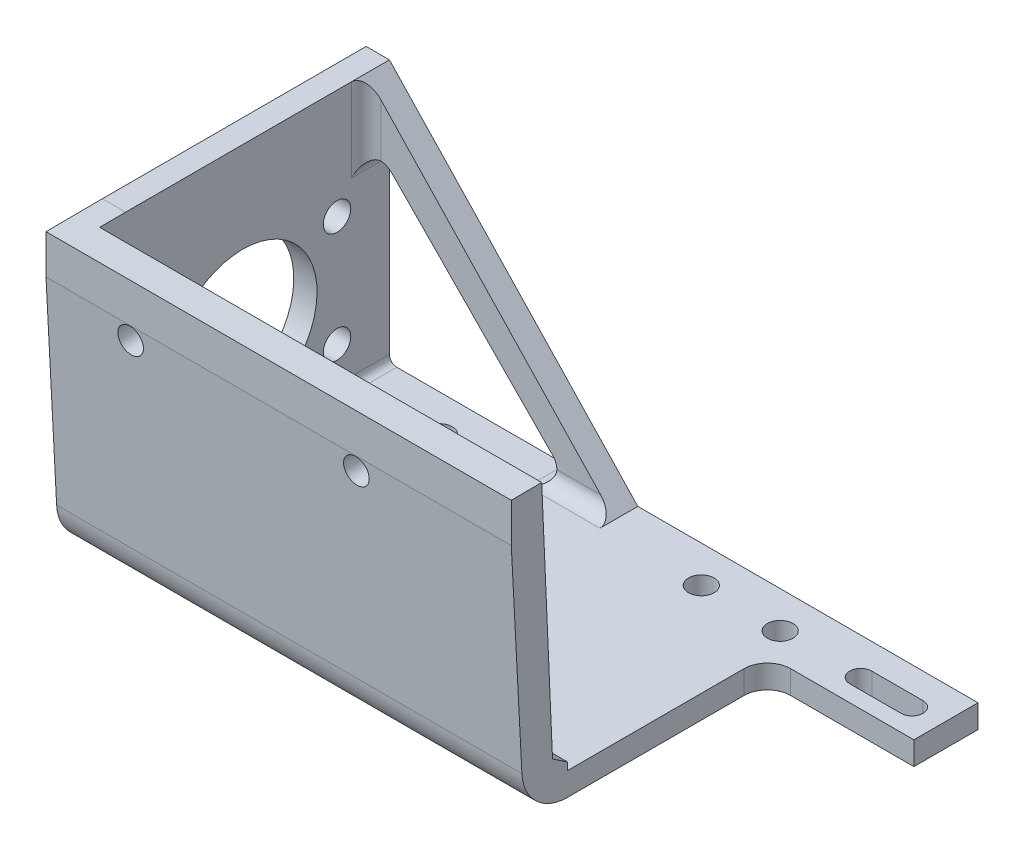
SolidWorks part; units mm, degrees
ref_plane "Front Plane" through (0, 0, 0) normal (0, 0, 1) x (1, 0, 0)
ref_plane "Top Plane" through (0, 0, 0) normal (0, 1, 0) x (1, 0, 0)
ref_plane "Right Plane" through (0, 0, 0) normal (1, 0, 0) x (0, 0, -1)
sketch "Sketch2" plane through (0, 0, 0) normal (0, 0, 1) x (1, 0, 0)
  line L0 (6.35, 78) -> (80, 0.1684)
  line L1 (0, 0) -> (6.35, 0)
  line L2 (0, 0) -> (0, 78)
  line L3 (0, 78) -> (6.35, 78)
  line L4 (6.35, 0) -> (6.35, 65.0327)
  line L6 (6.35, 65.0327) -> (70, 0.1684)
  line L7 (70, 0.1684) -> (80, 0.1684)
  dimension "D1" = 6.35
  dimension "D2" = 78
  dimension "D3" = 80
  dimension "D4" = 10
extrude "Boss-Extrude1" add sketch "Sketch2" along normal blind 80
sketch "Sketch3" plane through (6.35, 0, 0) normal (1, 0, 0) x (0, 0, -1)
  line L0 (0, 0) -> (0, 65.0327) construction
  line L1 (-80, 0) -> (0, 0)
  line L2 (-80, 0) -> (-80, 6.35)
  line L3 (-80, 6.35) -> (0, 6.35)
  line L4 (0, 0) -> (0, 6.35)
  dimension "D1" = 6.35
extrude "Boss-Extrude2" add sketch "Sketch3" along normal blind 160.65
sketch "Sketch8" plane through (0, 6.35, 0) normal (0, 1, 0) x (1, 0, 0)
  line L0 (167, 0) -> (74.1505, 0) construction
  line L1 (6.35, -80) -> (94.6764, -80)
  line L2 (6.35, -80) -> (6.35, -6.35)
  line L3 (6.35, -6.35) -> (94.6764, -6.35)
  line L4 (94.6764, -80) -> (94.6764, -6.35)
  dimension "D1" = 6.35
extrude "Cut-Extrude2" cut sketch "Sketch8" along normal up to next
sketch "Sketch9" plane through (0, 6.35, 0) normal (0, 1, 0) x (1, 0, 0)
  line L1 (167, -80) -> (0, -80)
  line L2 (167, -80) -> (167, -72)
  line L3 (167, -72) -> (0, -72)
  line L4 (0, -80) -> (0, -72)
extrude "Cut-Extrude4" cut sketch "Sketch9" against normal through all both and the other way through all
sketch "Sketch10" plane through (0, 6.35, 0) normal (0, 1, 0) x (1, 0, 0)
  line L0 (167, 0) -> (74.1505, 0) construction
  line L1 (167, -72) -> (127, -72)
  line L2 (167, -72) -> (167, -17.5)
  line L3 (167, -17.5) -> (127, -17.5)
  line L4 (127, -72) -> (127, -17.5)
  dimension "D1" = 17.5
extrude "Cut-Extrude5" cut sketch "Sketch10" against normal up to next
sketch "Sketch11" plane through (0, 6.35, 0) normal (0, 1, 0) x (1, 0, 0)
  line L0 (159, -10) -> (145, -10) construction
  line L1 (159, -13) -> (145, -13)
  line L2 (159, -7) -> (145, -7)
  line L3 (167, 0) -> (167, -17.5) construction
  line L4 (167, 0) -> (74.1505, 0) construction
  line L5 (0, -72) -> (0, 0) construction
  arc A0 (159, -13) -> (159, -7) centre (159, -10) ccw
  arc A1 (145, -7) -> (145, -13) centre (145, -10) ccw
  circle A2 centre (123, -10) radius 3.5
  circle A3 centre (101.48, -10) radius 3.5
  circle A6 centre (101.48, -62) radius 3.5
  circle A9 centre (30, -10) radius 3.5
  point P2 (152, -10)
  point P7 (162, -10)
  point P18 (0, 0)
  dimension "D1" = 14
  dimension "D4" = 30
  dimension "D5" = 22
  dimension "D9" = 65.52
  dimension "D2" = 5
  dimension "D3" = 7
extrude "Cut-Extrude6" cut sketch "Sketch11" against normal up to next
sketch "Sketch12" plane through (6.35, 0, 0) normal (1, 0, 0) x (0, 0, -1)
  line L0 (0, 6.35) -> (0, 65.0327) construction
  line L2 (0, 6.35) -> (-72, 6.35) construction
  circle A0 centre (-66.64, 15.3315) radius 3.75
  circle A1 centre (-66.64, 48.1711) radius 3.75
  circle A2 centre (-14.3, 48.12) radius 3.75
  circle A3 centre (-14.3, 17.9) radius 3.75
  circle A4 centre (-40, 33) radius 20.25
  dimension "D1" = 40
  dimension "D2" = 26.65
  dimension "D3" = 52.34
  dimension "D4" = 30.22
  dimension "D5" = 11.55
  dimension "D6" = 14.3
extrude "Cut-Extrude7" cut sketch "Sketch12" against normal up to next
fillet "Fillet1" radius 4 1 edges at (6.35, 71.5164, 6.35)
fillet "Fillet2" radius 4 1 edges at (6.35, 65.0327, 5.175)
fillet "Fillet3" radius 4 1 edges at (69.0423, 6.35, 6.35)
fillet "Fillet4" radius 4 1 edges at (63.9342, 6.35, 5.175)
fillet "Fillet5" radius 2 1 edges at (6.35, 6.35, 36)
fillet "Fillet6" radius 6.35 1 edges at (127, 3.175, 17.5)
sketch "Sketch17" plane through (0, 0, 0) normal (-1, 0, 0) x (0, 0, 1)
  line L0 (87.3842, 67.2065) -> (84.4829, 11.8458) construction
  line L1 (87.3842, 67.2065) -> (84.4829, 11.8458)
  line L2 (87.3842, 67.2065) -> (87.3842, 77.9122)
  line L3 (87.3842, 77.9122) -> (72, 78)
  line L4 (72, 78) -> (72, 0)
  arc A0 (72, 0) -> (84.4829, 11.8458) centre (72, 12.5) ccw construction
  arc A1 (72, 0) -> (84.4829, 11.8458) centre (72, 12.5) ccw
extrude "Boss-Extrude3" add sketch "Sketch17" against normal up to surface (6.35 mm away) up to face at (6.35, 51.9211, 66.64)
sketch "Sketch18" plane through (6.35, 0, 0) normal (1, 0, 0) x (0, 0, -1)
  line L0 (-87.3842, 77.9122) -> (-87.3842, 67.2065) construction
  line L1 (-87.3842, 67.2065) -> (-84.4829, 11.8458) construction
  line L2 (-87.3842, 77.9122) -> (-87.3842, 67.2065)
  line L3 (-87.3842, 67.2065) -> (-84.4829, 11.8458)
  line L4 (-87.3842, 77.9122) -> (-79.0854, 77.9596)
  line L5 (-72, 78) -> (-87.3842, 77.9122) construction
  line L6 (-79.0854, 77.9596) -> (-76.1342, 11.1534)
  line L7 (-76.1342, 11.1534) -> (-72, 8.35)
  line L8 (-72, 8.35) -> (-72, 0)
  arc A0 (-84.4829, 11.8458) -> (-72, 0) centre (-72, 12.5) ccw construction
  arc A1 (-84.4829, 11.8458) -> (-72, 0) centre (-72, 12.5) ccw
extrude "Boss-Extrude4" add sketch "Sketch18" along normal up to surface (120.65 mm away) up to face at (127, 3.175, 47.925)
sketch "Sketch20" plane through (0, -3.335, 75.4942) normal (0, 0.0441, -0.999) x (-1, 0, 0)
  line L0 (-127, 81.3738) -> (-6.35, 81.3738) construction
  circle A0 centre (-84.5356, 67.3238) radius 3.5
  circle A1 centre (-22.9043, 67.3238) radius 3.5
  point P6 (0, 0)
  dimension "D1" = 14.05
extrude "Cut-Extrude8" cut sketch "Sketch20" against normal up to surface (8.7638 mm away) up to face at (63.5, 39.5262, 85.9335)
